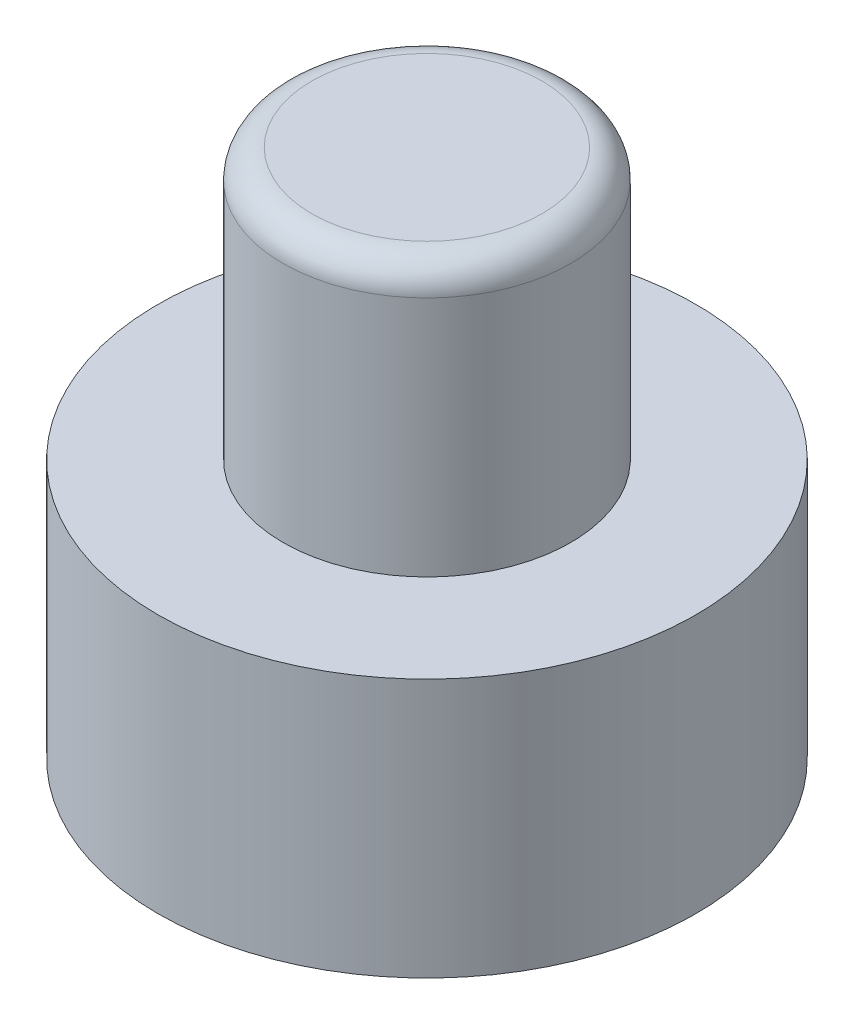
SolidWorks part; units mm, degrees
ref_plane "Front Plane" through (0, 0, 0) normal (0, 0, 1) x (1, 0, 0)
ref_plane "Top Plane" through (0, 0, 0) normal (0, 1, 0) x (1, 0, 0)
ref_plane "Right Plane" through (0, 0, 0) normal (1, 0, 0) x (0, 0, -1)
sketch "Sketch1" plane through (0, 0, 0) normal (0, 1, 0) x (1, 0, 0)
  circle A0 centre (0, 0) radius 4.675
  dimension "D1" = 9.35
extrude "Boss-Extrude1" add sketch "Sketch1" along normal blind 4.5
sketch "Sketch2" plane through (0, 4.5, 0) normal (0, 1, 0) x (1, 0, 0)
  circle A0 centre (0, 0) radius 2.5
  dimension "D1" = 5
extrude "Boss-Extrude2" add sketch "Sketch2" along normal blind 4.7
fillet "Fillet1" radius 0.5 1 edges at (0, 9.2, 2.5)
